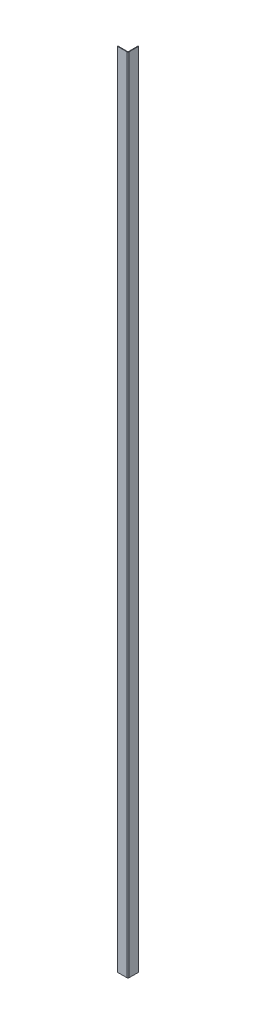
SolidWorks part; units mm, degrees
note: The reader was unsure of these and kept them because the rebuilt part matched: flange length of "Edge-Flange1".
material "Galvanized Steel"
ref_plane "Front" through (0, 0, 0) normal (0, 0, 1) x (1, 0, 0)
ref_plane "Top" through (0, 0, 0) normal (0, 1, 0) x (1, 0, 0)
ref_plane "Right" through (0, 0, 0) normal (1, 0, 0) x (0, 0, -1)
sketch "Sketch1" plane through (0, 0, 0) normal (1, 0, 0) x (0, 0, -1)
  line L1 (20, -1523.5) -> (-20, -1523.5)
  line L2 (20, -1523.5) -> (20, 1523.5)
  line L3 (20, 1523.5) -> (-20, 1523.5)
  line L4 (-20, -1523.5) -> (-20, 1523.5)
  line L5 (20, -1523.5) -> (-20, 1523.5) construction
  line L6 (20, 1523.5) -> (-20, -1523.5) construction
  point P0 (0, 0)
  dimension "D1" = 40
  dimension "D2" = 3047
base flange "Base-Flange1" sketch "Sketch1" thickness 2 reverse thickness direction no parameters "D1"=13
edge flange "Edge-Flange1" sketch "Sketch8" flange angle 90 flange length 40 flange position material inside bend radius 2.5 thickness 2 relief rectangular parameters "D6"=10
sketch "Sketch8" plane through (-2, 0, 20) normal (0, 0, -1) x (0, -1, 0)
  line L2 (-1523.5, 0) -> (-1523.5, 38)
  line L3 (-1523.5, 38) -> (1523.5, 38)
  line L4 (1523.5, 38) -> (1523.5, 0)
  line L5 (1523.5, 0) -> (-1523.5, 0) construction
  line L6 (1523.5, 0) -> (-1523.5, 0)
bend "EdgeBend1" bend radius 2.5 bend angle 90 parameters "D5"=1
sketch "Bend-Lines1" [suppressed] plane through (0, 0, 0) normal (0, 1, 0) x (1, 0, 0)
sketch "Bounding-Box1" [suppressed] plane through (0, 0, 0) normal (0, 1, 0) x (1, 0, 0)
sheet metal parameters "Sheet-Metal1" thickness 2 parameters "D1"=13
flat pattern "Flat-Pattern1" [suppressed]
sketch "Bend-Lines2" plane through (0, 0, 0) normal (0, 1, 0) x (1, 0, 0)
sketch3d "Bounding-Box2" [suppressed]
  line L0 (-20, 1500, 0) -> (-20, -1500, 0) construction
  line L1 (20, 1500, 0) -> (20, -1500, 0) construction
  line L2 (-20, 1500, 0) -> (20, 1500, 0) construction
  line L3 (-20, -1500, 0) -> (20, -1500, 0) construction
sheet metal parameters "Sheet-Metal2" thickness 2 parameters "D1"=13
flat pattern "Flat-Pattern1"
sketch "Bend-Lines2" plane through (0, 0, 0) normal (1, 0, 0) x (0, 0, -1)
  line L0 (-18.2489, 1523.5) -> (-18.2489, -1523.5) construction
  line L1 (-18.2489, 1523.5) -> (-18.2489, -1523.5) construction
sketch3d "Bounding-Box2" [suppressed]
  line L0 (20, 1523.5, 0) -> (20, -1523.5, 0) construction
  line L1 (-56.4978, 1523.5, 0) -> (-56.4978, -1523.5, 0) construction
  line L2 (20, 1523.5, 0) -> (-56.4978, 1523.5, 0) construction
  line L3 (20, -1523.5, 0) -> (-56.4978, -1523.5, 0) construction
bend of the flat pattern "Flatten-<EdgeBend1>1"
